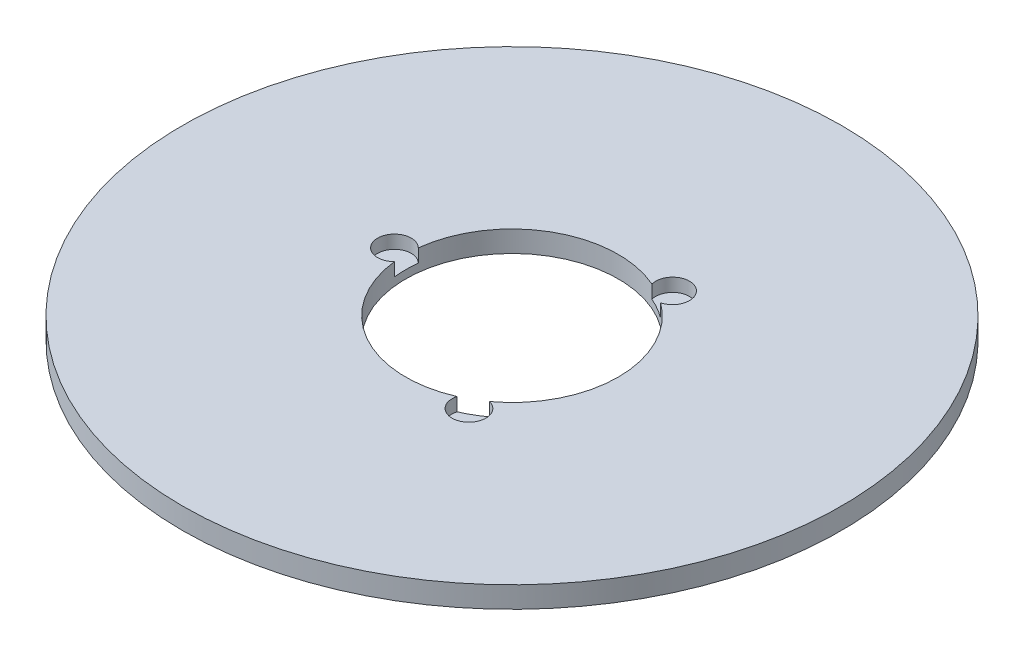
SolidWorks part; units mm, degrees
ref_plane "Front Plane" through (0, 0, 0) normal (0, 0, 1) x (1, 0, 0)
ref_plane "Top Plane" through (0, 0, 0) normal (0, 1, 0) x (1, 0, 0)
ref_plane "Right Plane" through (0, 0, 0) normal (1, 0, 0) x (0, 0, -1)
sketch "Sketch1" plane through (0, 0, 0) normal (0, 1, 0) x (1, 0, 0)
  circle A0 centre (0, 0) radius 77.5
  dimension "FLANGE_OD" = 155
extrude "Boss-Extrude1" add sketch "Sketch1" along normal blind 5
sketch "Sketch2" plane through (0, 0, 0) normal (0, 1, 0) x (1, 0, 0)
  circle A0 centre (0, 0) radius 25
  dimension "BORE_D" = 50
extrude "Cut-Extrude1" cut sketch "Sketch2" along normal through all
sketch "Sketch3" plane through (0, 5, 0) normal (0, 1, 0) x (1, 0, 0)
  circle A0 centre (0, 0) radius 27.6463 construction
  circle A1 centre (-27.6463, 0) radius 3.9683
  dimension "BOLT_D" = 7.9365
  dimension "BOLT_PCD" = 55.2926
extrude "Cut-Extrude2" cut sketch "Sketch3" against normal blind 3.1126
pattern_circular "CirPattern1" count 3 over 360 about axis through (0, 0, 0) along (0, 1, 0) of "Cut-Extrude2"
